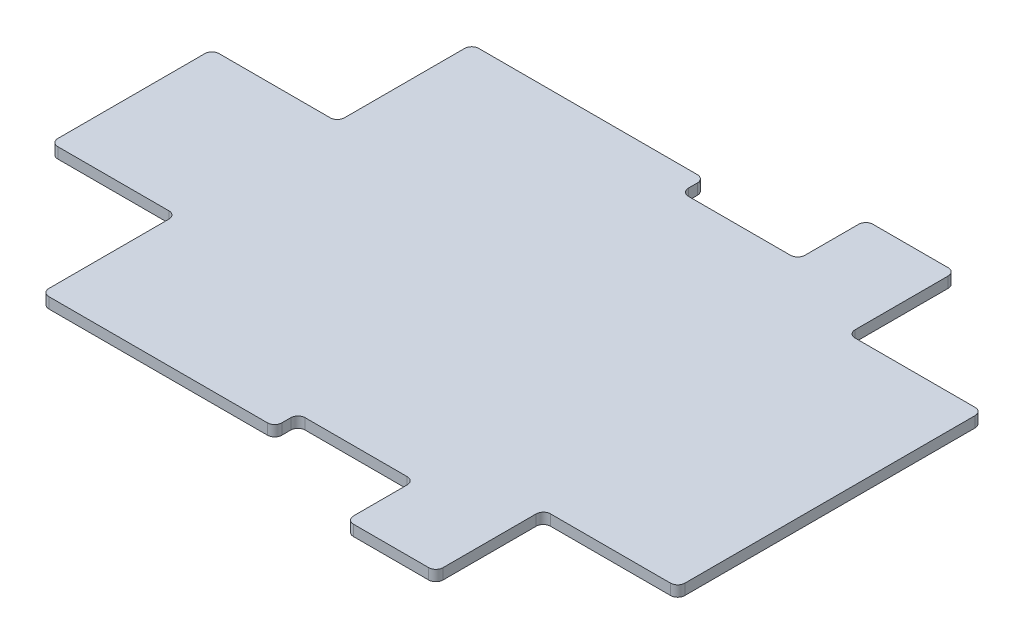
SolidWorks part; units mm, degrees
material "Aleación 1060"
ref_plane "Alzado" through (0, 0, 0) normal (0, 0, 1) x (1, 0, 0)
ref_plane "Planta" through (0, 0, 0) normal (0, 1, 0) x (1, 0, 0)
ref_plane "Vista lateral" through (0, 0, 0) normal (1, 0, 0) x (0, 0, -1)
sketch "Croquis1" plane through (0, 0, 0) normal (0, 1, 0) x (1, 0, 0)
  line L0 (0, 0) -> (-390, 0)
  line L1 (-390, 0) -> (-390, 45)
  line L2 (-390, 45) -> (-320, 45)
  line L3 (-320, 45) -> (-320, 120)
  line L4 (-320, 120) -> (-190, 120)
  line L5 (-190, 120) -> (-190, 107)
  line L6 (-190, 107) -> (-125, 107)
  line L7 (-125, 107) -> (-125, 145)
  line L8 (-125, 145) -> (-75, 145)
  line L9 (-75, 145) -> (-75, 85)
  line L10 (0, 0) -> (0, 85)
  line L11 (0, 85) -> (-75, 85)
  dimension "D1" = 390
  dimension "D2" = 45
  dimension "D3" = 75
  dimension "D4" = 120
  dimension "D5" = 130
  dimension "D6" = 13
  dimension "D7" = 50
  dimension "D8" = 85
  dimension "D9" = 65
  dimension "D10" = 60
extrude "Saliente-Extruir1" add sketch "Croquis1" along normal blind 6
mirror "Simetría1" about plane through (0, 6, 0) normal (0, 0, -1) of "Saliente-Extruir1"
fillet "Redondeo1" radius 4 20 edges at (-390, 3, -45) (-320, 3, -45) (-320, 3, -120) (-190, 3, -120) (-190, 3, -107) (-125, 3, -107) (-125, 3, -145) (-75, 3, -85) (-75, 3, -145) (0, 3, -85) (0, 3, 85) (-75, 3, 85) (-75, 3, 145) (-125, 3, 145) (-125, 3, 107) (-190, 3, 107) (-190, 3, 120) (-320, 3, 120) (-320, 3, 45) (-390, 3, 45)
sketch "Croquis2" plane through (0, 6, 0) normal (0, 1, 0) x (1, 0, 0)
  line L0 (-390, 0) -> (0, 0) construction
  line L1 (-390, 41) -> (-390, -41) construction
  line L2 (0, -81) -> (0, 81) construction
  line L3 (-214.7209, -131) -> (31.1095, -131) construction
  line L4 (-214.0485, -154) -> (44.3152, -154) construction
  line L5 (-79, -145) -> (-121, -145) construction
  line L6 (-44, -177) -> (-156, -177)
  line L7 (-44, -177) -> (-44, -131)
  line L8 (-44, -131) -> (-156, -131)
  line L9 (-156, -177) -> (-156, -131)
  line L10 (-44, -177) -> (-156, -131) construction
  line L11 (-44, -131) -> (-156, -177) construction
  line L12 (-156, 154) -> (-44, 154) construction
  line L13 (-374, -177) -> (-486, -177)
  line L14 (-374, -177) -> (-374, -131)
  line L15 (-374, -131) -> (-486, -131)
  line L16 (-486, -177) -> (-486, -131)
  line L17 (-374, -177) -> (-486, -131) construction
  line L18 (-374, -131) -> (-486, -177) construction
  line L19 (-44, 177) -> (-156, 177)
  line L20 (-44, 177) -> (-44, 131)
  line L21 (-44, 131) -> (-156, 131)
  line L22 (-156, 177) -> (-156, 131)
  line L23 (-374, 131) -> (-486, 177) construction
  line L24 (-374, 177) -> (-486, 131) construction
  line L25 (-486, 177) -> (-486, 131)
  line L26 (-374, 131) -> (-486, 131)
  line L27 (-374, 177) -> (-374, 131)
  line L28 (-374, 177) -> (-486, 177)
  line L29 (-430, -154) -> (-430, 154) construction
  point P10 (-100, -154)
  point P17 (-100, -145)
  point P20 (-430, -154)
  point P33 (-430, 154)
  dimension "D1" = 131
  dimension "D2" = 154
  dimension "D3" = 46
  dimension "D4" = 112
  dimension "D5" = 330
sketch "Croquis3" plane through (0, 6, 0) normal (0, 1, 0) x (1, 0, 0)
  line L0 (-100, -145) -> (-100, 145) construction
  line L1 (-79, -145) -> (-121, -145) construction
  line L2 (-79, 145) -> (-121, 145) construction
  line L3 (-161.61, 16.8885) -> (-161.61, -25.475) construction
  line L4 (-232.2, 27.5722) -> (-232.2, -25.475) construction
  dimension "D1" = 132.2
  dimension "D2" = 61.61
